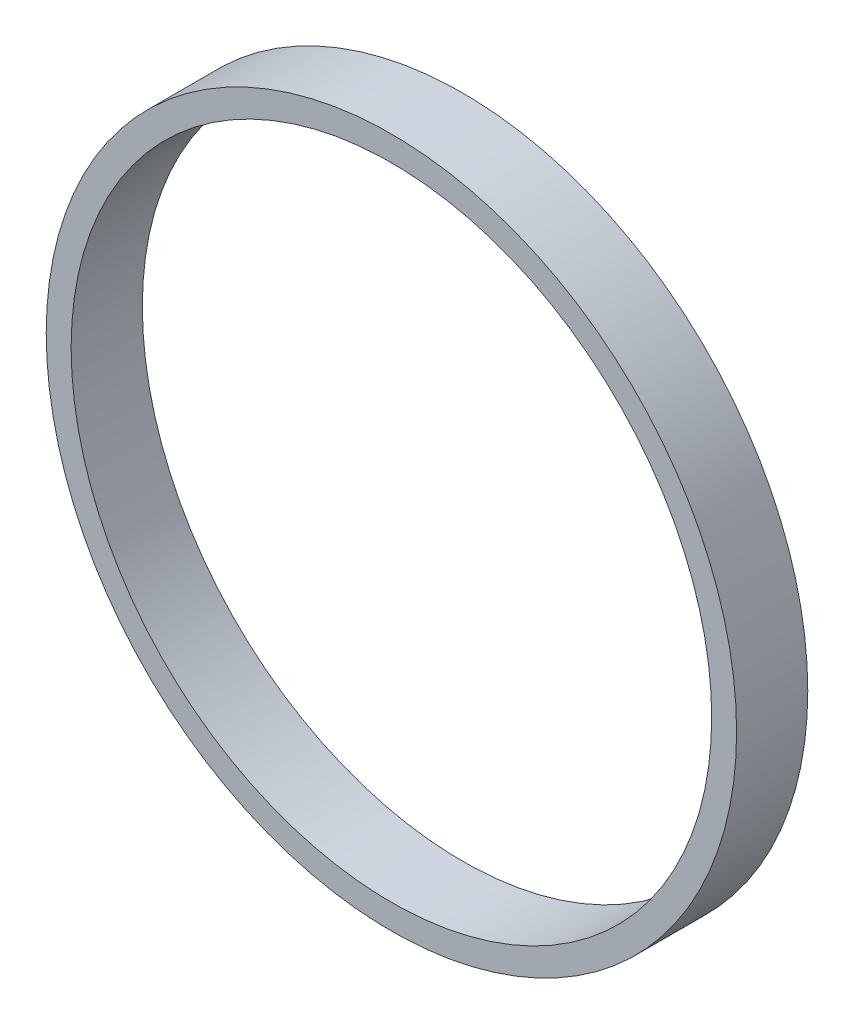
SolidWorks part; units mm, degrees
ref_plane "Płaszczyzna przednia" through (0, 0, 0) normal (0, 0, 1) x (1, 0, 0)
ref_plane "Płaszczyzna górna" through (0, 0, 0) normal (0, 1, 0) x (1, 0, 0)
ref_plane "Płaszczyzna prawa" through (0, 0, 0) normal (1, 0, 0) x (0, 0, -1)
sketch "Szkic1" plane through (0, 0, 0) normal (0, 0, 1) x (1, 0, 0)
  circle A0 centre (0, 0) radius 45
  circle A1 centre (0, 0) radius 48.5
  dimension "D1" = 90
  dimension "D2" = 3.5
extrude "Dodanie-wyciągnięcie1" add sketch "Szkic1" along normal blind 10
